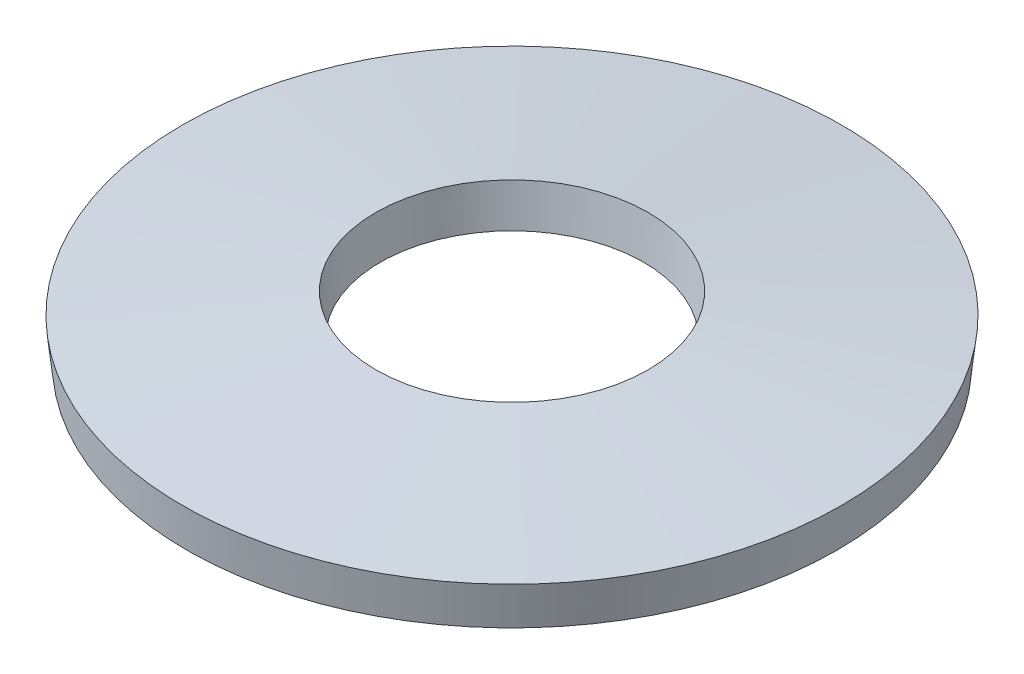
SolidWorks part; units mm, degrees
material "Cast Alloy Steel"
ref_plane "Front Plane" through (0, 0, 0) normal (0, 0, 1) x (1, 0, 0)
ref_plane "Top Plane" through (0, 0, 0) normal (0, 1, 0) x (1, 0, 0)
ref_plane "Right Plane" through (0, 0, 0) normal (1, 0, 0) x (0, 0, -1)
sketch "Sketch1" plane through (0, 0, 0) normal (0, 0, 1) x (1, 0, 0)
  line L0 (0, -0.9273) -> (0, 0.9273) construction
  line L1 (3.9464, 0) -> (4, 0.4971)
  line L2 (4, 0.4971) -> (1.6536, 0.75)
  line L3 (1.6536, 0.75) -> (1.6, 0.2529)
  line L4 (1.6, 0.2529) -> (3.9464, 0)
  point P5 (0, 0)
  point P8 (2.8871, 1.3584)
  point P9 (1.916, 1.6231)
  point P10 (1.7253, 1.0731)
  dimension "D1" = 3.2
  dimension "D2" = 8
  dimension "D3" = 0.5
  dimension "D4" = 0.75
revolve "Revolve1" add sketch "Sketch1" angle 360 about L0
